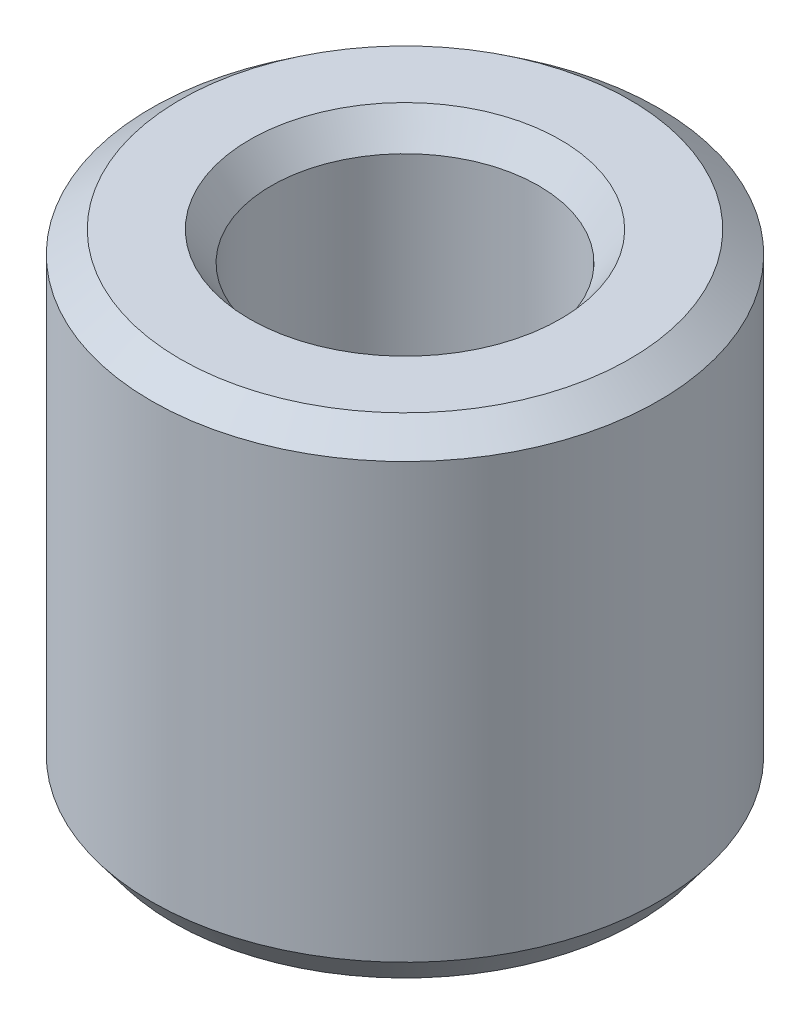
SolidWorks part; units mm, degrees
ref_plane "Front Plane" through (0, 0, 0) normal (0, 0, 1) x (1, 0, 0)
ref_plane "Top Plane" through (0, 0, 0) normal (0, 1, 0) x (1, 0, 0)
ref_plane "Right Plane" through (0, 0, 0) normal (1, 0, 0) x (0, 0, -1)
sketch "Sketch1" plane through (0, 0, 0) normal (0, 1, 0) x (1, 0, 0)
  circle A0 centre (0, 0) radius 30
  dimension "SLEEVE_OD" = 60
extrude "Boss-Extrude1" add sketch "Sketch1" along normal blind 57.2841
sketch "Sketch2" plane through (0, 0, 0) normal (0, 1, 0) x (1, 0, 0)
  circle A0 centre (0, 0) radius 15.8059
  dimension "BORE_D" = 31.6118
extrude "Cut-Extrude1" cut sketch "Sketch2" along normal through all
chamfer "Chamfer1" distance 2.5676 angle 53.144 4 edges at (0, 57.2841, 15.8059) (0, 0, 15.8059) (0, 0, 30) (0, 57.2841, 30) first distance on face at (0, 57.2841, 15.8059) first distance on face at (0, 0, 15.8059) first distance on face at (0, 57.2841, 30)
